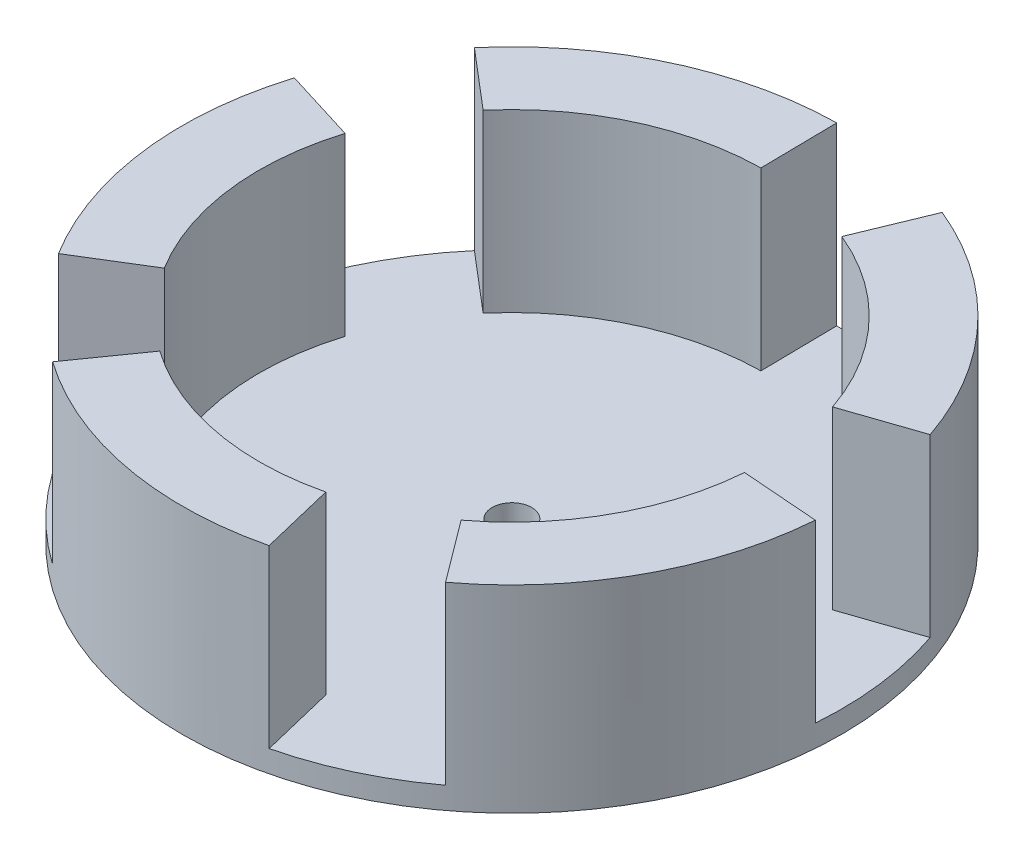
SolidWorks part; units mm, degrees
ref_plane "Front Plane" through (0, 0, 0) normal (0, 0, 1) x (1, 0, 0)
ref_plane "Top Plane" through (0, 0, 0) normal (0, 1, 0) x (1, 0, 0)
ref_plane "Right Plane" through (0, 0, 0) normal (1, 0, 0) x (0, 0, -1)
sketch "Sketch3" plane through (0, 0, 0) normal (0, 1, 0) x (1, 0, 0)
  circle A0 centre (0, 0) radius 30
  dimension "D2" = 60
extrude "Boss-Extrude3" add sketch "Sketch3" along normal blind 2
sketch "Sketch4" plane through (0, 2, 0) normal (0, 1, 0) x (1, 0, 0)
  line L0 (0, 0) -> (-17.5189, 14.9027) construction
  line L1 (0, 0) -> (8.7596, 21.2666) construction
  line L2 (0, 0) -> (21.7702, 7.4201) construction
  line L3 (0, 0) -> (22.9326, -1.7592) construction
  line L4 (0, 0) -> (13.7843, -18.4118) construction
  line L5 (0, 0) -> (5.4135, -22.3538) construction
  line L6 (0, 0) -> (-13.251, -18.7992) construction
  line L7 (0, 0) -> (-19.5869, -12.0563) construction
  line L8 (0, 0) -> (-21.9739, 6.7932) construction
  line L9 (0, 0) -> (-0.3296, 22.9976) construction
  line L10 (-17.5189, 14.9027) -> (-0.3296, 22.9976) construction
  line L11 (-0.3296, 22.9976) -> (8.7596, 21.2666) construction
  line L12 (8.7596, 21.2666) -> (21.7702, 7.4201) construction
  line L13 (21.7702, 7.4201) -> (22.9326, -1.7592) construction
  line L14 (22.9326, -1.7592) -> (13.7843, -18.4118) construction
  line L15 (13.7843, -18.4118) -> (5.4135, -22.3538) construction
  line L16 (5.4135, -22.3538) -> (-13.251, -18.7992) construction
  line L17 (-13.251, -18.7992) -> (-19.5869, -12.0563) construction
  line L18 (-19.5869, -12.0563) -> (-21.9739, 6.7932) construction
  line L19 (-21.9739, 6.7932) -> (-17.5189, 14.9027) construction
  line L20 (13.7843, -18.4118) -> (17.9795, -24.0153)
  line L21 (22.9326, -1.7592) -> (29.9121, -2.2946)
  line L22 (21.7702, 7.4201) -> (28.3959, 9.6784)
  line L23 (8.7596, 21.2666) -> (11.4256, 27.7391)
  line L24 (-0.3296, 22.9976) -> (-0.4299, 29.9969)
  line L25 (-17.5189, 14.9027) -> (-22.8507, 19.4383)
  line L26 (-21.9739, 6.7932) -> (-28.6616, 8.8607)
  line L27 (-19.5869, -12.0563) -> (-25.5481, -15.7255)
  line L28 (-13.251, -18.7992) -> (-17.284, -24.5207)
  line L29 (5.4135, -22.3538) -> (7.0611, -29.1572)
  circle A0 centre (0, 0) radius 23 construction
  arc A1 (-17.5189, 14.9027) -> (-0.3296, 22.9976) centre (0, 0) cw
  arc A2 (8.7596, 21.2666) -> (21.7702, 7.4201) centre (0, 0) cw
  arc A3 (22.9326, -1.7592) -> (13.7843, -18.4118) centre (0, 0) cw
  arc A4 (-13.251, -18.7992) -> (5.4135, -22.3538) centre (0, 0) ccw
  arc A5 (-19.5869, -12.0563) -> (-21.9739, 6.7932) centre (0, 0) cw
  arc A6 (-0.4299, 29.9969) -> (-22.8507, 19.4383) centre (0, 0) ccw
  arc A7 (-28.6616, 8.8607) -> (-25.5481, -15.7255) centre (0, 0) ccw
  arc A8 (7.0611, -29.1572) -> (-17.284, -24.5207) centre (0, 0) cw
  arc A9 (11.4256, 27.7391) -> (28.3959, 9.6784) centre (0, 0) cw
  arc A10 (29.9121, -2.2946) -> (17.9795, -24.0153) centre (0, 0) cw
  circle A11 centre (0, 0) radius 30 construction
  dimension "D1" = 46
  dimension "D2" = 19
extrude "Boss-Extrude4" add sketch "Sketch4" along normal blind 16
sketch "Sketch5" plane through (0, 0, 0) normal (0, -1, 0) x (1, 0, 0)
  line L7 (7.1176, -0.7704) -> (4.2259, 5.7788)
  line L8 (4.2259, 5.7788) -> (-2.8916, 6.5492)
  line L9 (-2.8916, 6.5492) -> (-7.1176, 0.7704)
  line L10 (-7.1176, 0.7704) -> (-4.2259, -5.7788)
  line L11 (-4.2259, -5.7788) -> (2.8916, -6.5492)
  line L12 (2.8916, -6.5492) -> (7.1176, -0.7704)
  circle A7 centre (0, 0) radius 6.2 construction
  circle A8 centre (0, 0) radius 8.5
  dimension "D1" = 12.4
  dimension "D2" = 17
extrude "Boss-Extrude5" add sketch "Sketch5" along normal blind 8
sketch "Sketch6" plane through (0, 0, 0) normal (0, -1, 0) x (1, 0, 0)
  circle A0 centre (0, 0) radius 1.8
  dimension "D1" = 3.6
extrude "Cut-Extrude1" cut sketch "Sketch6" against normal blind 5
fillet "Fillet1" radius 2 1 edges at (0, 0, 8.5)
